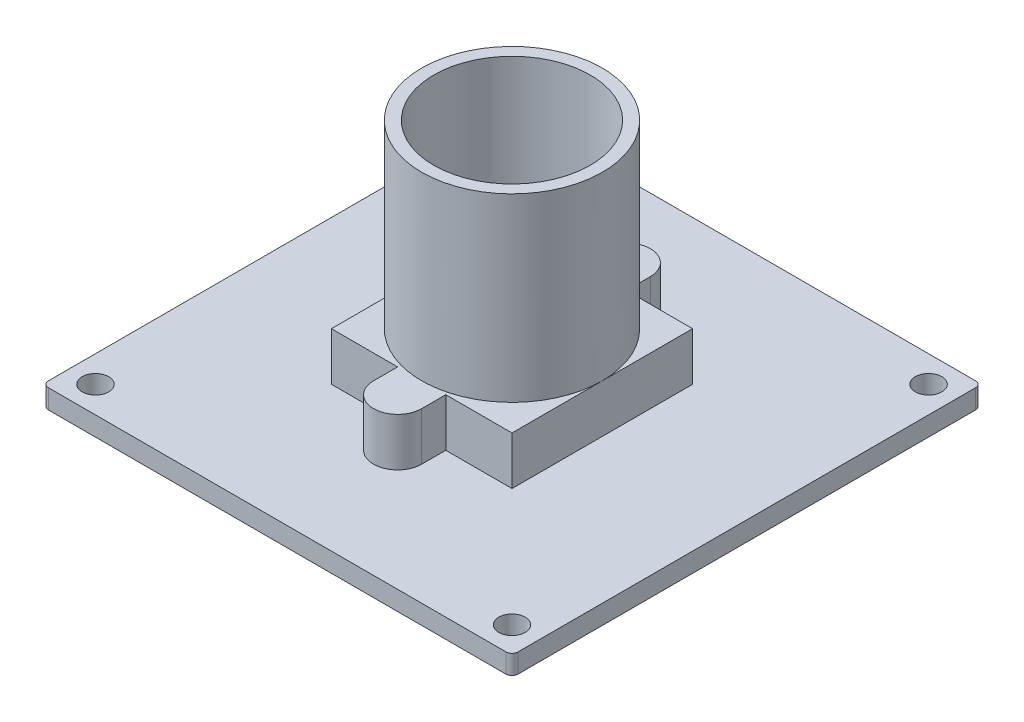
SolidWorks part; units mm, degrees
material "FR4_stuffedProtoboard"
ref_plane "Front Plane" through (0, 0, 0) normal (0, 0, 1) x (1, 0, 0)
ref_plane "Top Plane" through (0, 0, 0) normal (0, 1, 0) x (1, 0, 0)
ref_plane "Right Plane" through (0, 0, 0) normal (1, 0, 0) x (0, 0, -1)
sketch "Sketch1" plane through (0, 0, 0) normal (0, 1, 0) x (1, 0, 0)
  line L1 (-19.5, 19.5) -> (19.5, 19.5)
  line L2 (-19.5, 19.5) -> (-19.5, -19.5)
  line L3 (-19.5, -19.5) -> (19.5, -19.5)
  line L4 (19.5, 19.5) -> (19.5, -19.5)
  line L5 (-19.5, 19.5) -> (19.5, -19.5) construction
  line L6 (-19.5, -19.5) -> (19.5, 19.5) construction
  point P0 (0, 0)
  dimension "D1" = 39
  dimension "D2" = 39
extrude "Boss-Extrude1" add sketch "Sketch1" along normal mid plane 1.6
fillet "Fillet1" radius 0.5 4 edges at (-19.5, 0, 19.5) (19.5, 0, 19.5) (19.5, 0, -19.5) (-19.5, 0, -19.5)
sketch "Sketch2" plane through (0, 0.8, 0) normal (0, 1, 0) x (1, 0, 0)
  line L0 (19, 19.5) -> (-19, 19.5) construction
  line L1 (-19.5, 19) -> (-19.5, -19) construction
  line L2 (0, 19.5) -> (0, -19.5) construction
  line L3 (-19, -19.5) -> (19, -19.5) construction
  line L4 (-19.5, 0) -> (19.5, 0) construction
  line L5 (19.5, -19) -> (19.5, 19) construction
  circle A0 centre (-17.3, 17.3) radius 1.1
  circle A1 centre (-17.3, -17.3) radius 1.1
  circle A2 centre (17.3, -17.3) radius 1.1
  circle A3 centre (17.3, 17.3) radius 1.1
  dimension "D1" = 2.2
  dimension "D2" = 2.2
  dimension "D3" = 2.2
extrude "Cut-Extrude1" cut sketch "Sketch2" against normal blind 1.6
sketch "Sketch3" plane through (0, 0.8, 0) normal (0, 1, 0) x (1, 0, 0)
  line L1 (-3.5, 3.5) -> (3.5, 3.5)
  line L2 (-3.5, 3.5) -> (-3.5, -3.5)
  line L3 (-3.5, -3.5) -> (3.5, -3.5)
  line L4 (3.5, 3.5) -> (3.5, -3.5)
  line L5 (-3.5, 3.5) -> (3.5, -3.5) construction
  line L6 (-3.5, -3.5) -> (3.5, 3.5) construction
  point P0 (0, 0)
  dimension "D1" = 7
  dimension "D2" = 7
extrude "Boss-Extrude2" add sketch "Sketch3" along normal blind 2
sketch "Sketch4" plane through (0, 0.8, 0) normal (0, 1, 0) x (1, 0, 0)
  line L0 (-2, 9.5) -> (-2, 7.5)
  line L1 (-7.5, 7.5) -> (-2, 7.5)
  line L2 (-7.5, 7.5) -> (-7.5, -7.5)
  line L3 (-7.5, -7.5) -> (-2, -7.5)
  line L4 (7.5, 7.5) -> (7.5, -7.5)
  line L5 (-7.5, 7.5) -> (7.5, -7.5) construction
  line L6 (-7.5, -7.5) -> (7.5, 7.5) construction
  line L7 (7, -7) -> (-7, -7)
  line L8 (7, -7) -> (7, 7)
  line L9 (7, 7) -> (-7, 7)
  line L10 (-7, -7) -> (-7, 7)
  line L11 (7, -7) -> (-7, 7) construction
  line L12 (7, 7) -> (-7, -7) construction
  line L13 (2, 9.5) -> (2, 7.5)
  line L14 (2, 7.5) -> (7.5, 7.5)
  line L15 (-7, 0) -> (7, 0) construction
  line L16 (2, -9.5) -> (2, -7.5)
  line L17 (-2, -9.5) -> (-2, -7.5)
  line L18 (2, -7.5) -> (7.5, -7.5)
  arc A0 (2, 9.5) -> (-2, 9.5) centre (0, 9.5) ccw
  arc A1 (2, -9.5) -> (-2, -9.5) centre (0, -9.5) cw
  point P0 (0, 0)
  point P6 (0, 0)
  dimension "D4" = 4
  dimension "D5" = 2
  dimension "D1" = 15
  dimension "D2" = 15
  dimension "D3" = 0.5
extrude "Boss-Extrude3" add sketch "Sketch4" along normal blind 4
sketch "Sketch5" plane through (0, 4.8, 0) normal (0, 1, 0) x (1, 0, 0)
  line L1 (-7.5, 7.5) -> (7.5, 7.5)
  line L2 (-7.5, 7.5) -> (-7.5, -7.5)
  line L3 (-7.5, -7.5) -> (7.5, -7.5)
  line L4 (7.5, 7.5) -> (7.5, -7.5)
  line L5 (-7.5, 7.5) -> (7.5, -7.5) construction
  line L6 (-7.5, -7.5) -> (7.5, 7.5) construction
  point P1 (0, 0)
extrude "Boss-Extrude4" add sketch "Sketch5" against normal blind 0.1
sketch "Sketch6" plane through (0, 4.8, 0) normal (0, 1, 0) x (1, 0, 0)
  line L0 (7.5, -7.5) -> (7.5, 7.5) construction
  circle A0 centre (0, 0) radius 7.5
extrude "Boss-Extrude5" add sketch "Sketch6" along normal blind 15
hole_wizard "M12 Clearance Hole1" positions "Sketch9" profile "Sketch10" hole size "M12" standard "ISO" end condition up to next
sketch "Sketch9" plane through (0, 19.8, 0) normal (0, 1, 0) x (1, 0, 0)
  point P0 (0, 0)
sketch "Sketch10" plane through (0, 19.8, 0) normal (1, 0, 0) x (0, 0, 1)
  line L0 (0, 0) -> (0, 15.1)
  line L1 (0, 15.1) -> (6.5, 15.1)
  line L2 (6.5, 15.1) -> (6.5, 0)
  line L5 (6.5, 0) -> (0, 0)
  line L11 (0, -6.35) -> (0, 107.95) construction
  dimension "Thru Hole Dia." = 13
  dimension "Thru Hole Depth" = 15.1
